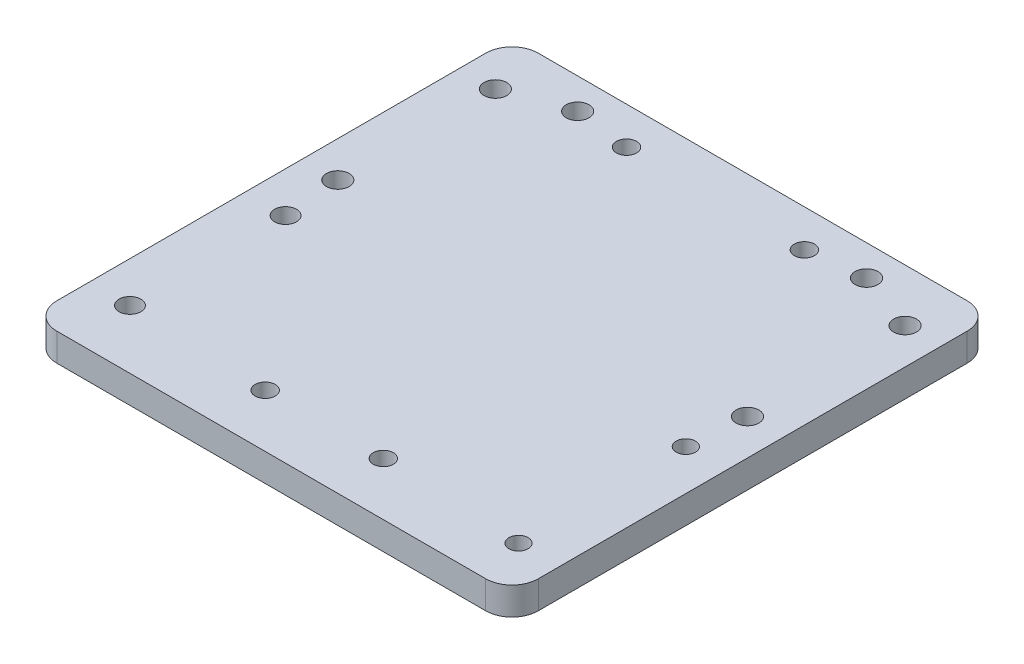
SolidWorks part; units mm, degrees
ref_plane "Front Plane" through (0, 0, 0) normal (0, 0, 1) x (1, 0, 0)
ref_plane "Top Plane" through (0, 0, 0) normal (0, 1, 0) x (1, 0, 0)
ref_plane "Right Plane" through (0, 0, 0) normal (1, 0, 0) x (0, 0, -1)
sketch "Sketch1" plane through (0, 0, 0) normal (0, 1, 0) x (1, 0, 0)
  line L1 (-27.5, 27.5) -> (27.5, 27.5)
  line L2 (-27.5, 27.5) -> (-27.5, -27.5)
  line L3 (-27.5, -27.5) -> (27.5, -27.5)
  line L4 (27.5, 27.5) -> (27.5, -27.5)
  line L5 (-27.5, 27.5) -> (27.5, -27.5) construction
  line L6 (-27.5, -27.5) -> (27.5, 27.5) construction
  point P0 (0, 0)
  dimension "D1" = 55
  dimension "D2" = 55
extrude "Boss-Extrude1" add sketch "Sketch1" along normal blind 3.175
sketch "Sketch2" plane through (0, 3.175, 0) normal (0, 1, 0) x (1, 0, 0)
  line L0 (0, 27.5) -> (0, -27.5) construction
  line L1 (27.5, 27.5) -> (-27.5, 27.5) construction
  line L2 (-27.5, -27.5) -> (27.5, -27.5) construction
  line L3 (-27.5, 27.5) -> (-27.5, -27.5) construction
  circle A0 centre (-23.4, 21.5) radius 1.3
  circle A1 centre (-23.4, 3.5) radius 1.3
  circle A2 centre (23.4, 3.5) radius 1.3
  circle A3 centre (23.4, 21.5) radius 1.3
  point P11 (-22.1, 21.5)
  point P17 (22.1, 21.5)
  dimension "D1" = 2.6
  dimension "D2" = 18
  dimension "D3" = 5.4
  dimension "D4" = 6
extrude "Cut-Extrude1" cut sketch "Sketch2" against normal up to surface (3.175 mm away) up to face at (0, 0, 0)
fillet "Fillet1" radius 3 4 edges at (-27.5, 1.5875, 27.5) (27.5, 1.5875, 27.5) (27.5, 1.5875, -27.5) (-27.5, 1.5875, -27.5)
sketch "Sketch3" plane through (0, 3.175, 0) normal (0, 1, 0) x (1, 0, 0)
  line L0 (-27.5, 0) -> (27.5, 0) construction
  line L1 (-22.865, -3) -> (22.855, -3) construction
  line L2 (-22.865, -3) -> (-22.865, -20.78) construction
  line L3 (-22.865, -20.78) -> (22.855, -22.11) construction
  line L4 (22.855, -3) -> (22.855, -22.11) construction
  line L5 (-27.5, 24.5) -> (-27.5, -24.5) construction
  line L6 (27.5, -24.5) -> (27.5, 24.5) construction
  circle A0 centre (-22.865, -3) radius 1.25
  circle A1 centre (22.855, -3) radius 1.1
  circle A2 centre (22.855, -22.11) radius 1.1
  circle A3 centre (-22.865, -20.78) radius 1.25
  dimension "D1" = 2.5
  dimension "D6" = 2.2
  dimension "D2" = 45.72
  dimension "D3" = 17.78
  dimension "D4" = 19.11
  dimension "D5" = 45.72
  dimension "D7" = 3
extrude "Cut-Extrude2" cut sketch "Sketch3" against normal up to surface (3.175 mm away) up to face at (23.4, 0, -20.2)
sketch "Sketch4" plane through (0, 3.175, 0) normal (0, 1, 0) x (1, 0, 0)
  line L0 (24.5, 27.5) -> (-24.5, 27.5) construction
  line L1 (-10.16, 23.24) -> (10.16, 23.24) construction
  line L2 (-10.16, 23.24) -> (-10.16, 8) construction
  line L3 (-10.16, 8) -> (10.16, 8) construction
  line L4 (10.16, 23.24) -> (10.16, 8) construction
  line L5 (-10.16, 23.24) -> (10.16, 8) construction
  line L6 (-10.16, 8) -> (10.16, 23.24) construction
  line L7 (0, 27.5) -> (0, -27.5) construction
  line L8 (-24.5, -27.5) -> (24.5, -27.5) construction
  circle A0 centre (-10.16, 23.24) radius 1.15
  circle A1 centre (10.16, 23.24) radius 1.15
  point P0 (0, 15.62)
  point P13 (0, 0)
  dimension "D1" = 2.3
  dimension "D2" = 20.32
  dimension "D3" = 15.24
  dimension "D4" = 8
extrude "Cut-Extrude3" cut sketch "Sketch4" against normal up to surface (3.175 mm away) up to face at (-22.865, 0, 22.03)
sketch "Sketch5" plane through (0, 3.175, 0) normal (0, 1, 0) x (1, 0, 0)
  line L0 (0, 27.5) -> (0, -27.5) construction
  line L1 (24.5, 27.5) -> (-24.5, 27.5) construction
  line L2 (-24.5, -27.5) -> (24.5, -27.5) construction
  circle A0 centre (-6.75, -21.45) radius 1.15
  circle A1 centre (6.75, -21.45) radius 1.15
  dimension "D1" = 2.3
  dimension "D2" = 6.75
  dimension "D3" = 6.05
extrude "Cut-Extrude4" cut sketch "Sketch5" against normal up to surface (3.175 mm away) up to face at (-10.16, 0, -22.09)
sketch "Sketch6" plane through (0, 3.175, 0) normal (0, 1, 0) x (1, 0, 0)
  line L0 (0, 27.5) -> (0, -27.5) construction
  line L1 (24.5, 27.5) -> (-24.5, 27.5) construction
  line L2 (-24.5, -27.5) -> (24.5, -27.5) construction
  circle A0 centre (-16.5, 24) radius 1.3
  circle A1 centre (16.5, 24) radius 1.3
  dimension "D1" = 2.6
  dimension "D2" = 16.5
  dimension "D3" = 3.5
extrude "Cut-Extrude5" cut sketch "Sketch6" against normal up to surface (3.175 mm away) up to face at (-6.75, 0, 22.6)
